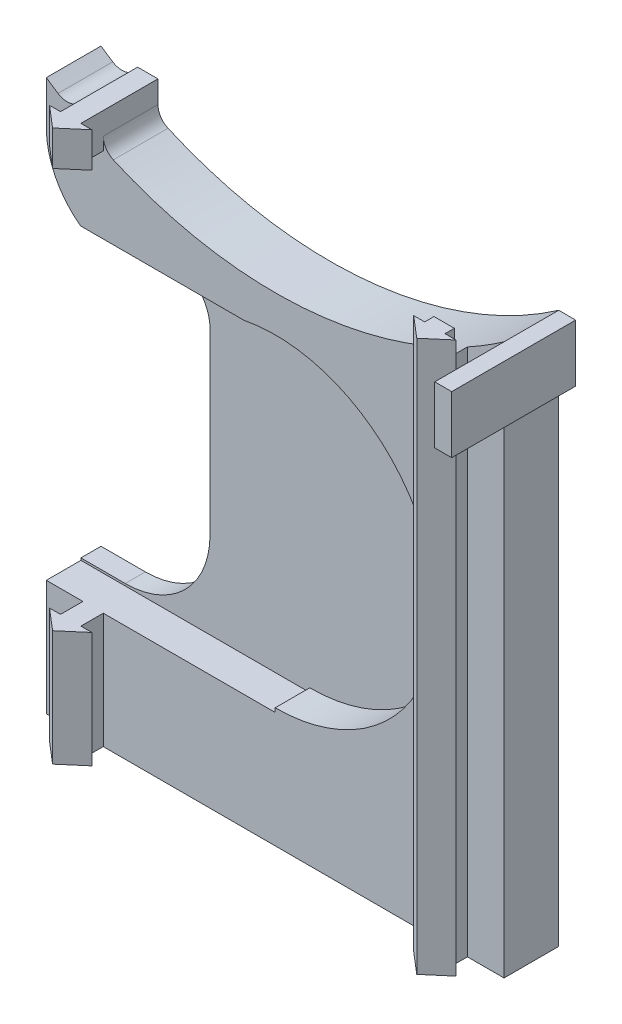
SolidWorks part; units mm, degrees
ref_plane "Alzado" through (0, 0, 0) normal (0, 0, 1) x (1, 0, 0)
ref_plane "Planta" through (0, 0, 0) normal (0, 1, 0) x (1, 0, 0)
ref_plane "Vista lateral" through (0, 0, 0) normal (1, 0, 0) x (0, 0, -1)
sketch "Croquis1" plane through (0, 0, 0) normal (0, 1, 0) x (1, 0, 0)
  line L16 (-22.8311, -9.1001) -> (-21.5393, -9.1001)
  line L17 (-19.1393, -6.4534) -> (-19.1393, -9.1001)
  line L18 (-21.5393, -6.4534) -> (-21.5393, -9.1001)
  line L19 (-19.1393, -9.1001) -> (-17.8476, -9.1001)
  line L20 (-22.8311, -9.1001) -> (-20.3393, -11.2322)
  line L21 (-20.3393, -11.2322) -> (-17.8476, -9.1001)
  line L23 (1.1429, 0) -> (1.1429, -6) construction
  line L35 (-23.6393, -8.8034) -> (-20.3393, -11.627) construction
  line L36 (-20.3393, -11.627) -> (-17.0393, -8.8034) construction
  line L38 (-21.8393, -6.4534) -> (-21.8393, -8.8034) construction
  line L39 (-18.8393, -6.4534) -> (-18.8393, -8.8034) construction
  line L40 (-18.8393, -8.8034) -> (-17.0393, -8.8034) construction
  line L42 (-25.8571, 0) -> (-25.8571, -6.4534)
  line L44 (-25.8571, 0) -> (28.1429, 0)
  line L45 (28.1429, 0) -> (28.1429, -6.4534)
  line L46 (21.4252, -6.4534) -> (21.4252, -9.1001)
  line L47 (21.4252, -9.1001) -> (20.1334, -9.1001)
  line L48 (22.6252, -11.2322) -> (20.1334, -9.1001)
  line L49 (25.117, -9.1001) -> (22.6252, -11.2322)
  line L50 (25.117, -9.1001) -> (23.8252, -9.1001)
  line L51 (23.8252, -6.4534) -> (23.8252, -9.1001)
  line L52 (-25.8571, -6.4534) -> (-21.5393, -6.4534)
  line L53 (-19.1393, -6.4534) -> (21.4252, -6.4534)
  line L54 (23.8252, -6.4534) -> (28.1429, -6.4534)
  point P10 (0, -5.8984)
  point P11 (-20.9906, -10.0474)
  point P24 (-18.6893, -10.2152)
  point P30 (20.9906, -10.0474)
  dimension "D2" = 0.3
  dimension "D4" = 0.3
  dimension "D5" = 0.2967
  dimension "D6" = 0.3
  dimension "D7" = 0.3
extrude "Saliente-Extruir1" add sketch "Croquis1" along normal blind 100
ref_plane "Plane1" through (0, 100, 0) normal (0, 1, 0) x (1, 0, 0)
sketch "Sketch3" plane through (-25.8571, 0, 0) normal (-1, 0, 0) x (0, 0, 1)
  line L1 (13.0991, 86.8623) -> (2.3754, 86.8623)
  line L2 (13.0991, 86.8623) -> (13.0991, 48.6348)
  line L3 (13.0991, 48.6348) -> (2.3754, 48.6348)
  line L4 (2.3754, 86.8623) -> (2.3754, 48.6348)
  point P6 (0, 0)
  point P7 (0, 0)
extrude "Cut-Extrude1" cut sketch "Sketch3" against normal blind 27
sketch "Sketch5" plane through (0, 0, 6.4534) normal (0, 0, 1) x (1, 0, 0)
  line L0 (1.1429, 48.6348) -> (1.1429, 86.8623) construction
  circle A0 centre (1.1429, 68.1655) radius 19.0562
  point P4 (1.1429, 68.1655)
extrude "Cut-Extrude2" cut sketch "Sketch5" against normal up to surface (4.078 mm away) up to face at (-12.3571, 67.7486, 2.3754)
sketch "Sketch6" plane through (0, 0, 0) normal (0, 0, -1) x (-1, 0, 0)
  line L0 (-28.1429, 100) -> (25.8571, 100) construction
  arc A0 (-28.1429, 100) -> (25.8571, 100) centre (-1.1429, 138.7173) ccw
  arc A1 (-28.1429, 100) -> (25.8571, 100) centre (-1.1429, 64.6987) cw
extrude "Cut-Extrude3" cut sketch "Sketch6" against normal blind 8
sketch "Sketch7" plane through (0, 0, 0) normal (0, 0, -1) x (-1, 0, 0)
  line L0 (25.8571, 100) -> (25.8571, 0) construction
  line L1 (25.8571, 48.8854) -> (10.6195, 48.8854)
  line L2 (25.8571, 48.8854) -> (25.8571, 84.8851)
  line L3 (25.8571, 84.8851) -> (10.6195, 84.8851)
  line L4 (10.6195, 48.8854) -> (10.6195, 84.8851)
extrude "Cut-Extrude4" cut sketch "Sketch7" against normal blind 5.8
fillet "Fillet1" radius 10 1 edges at (-25.8571, 84.8851, 1.1877)
fillet "Fillet2" radius 10 1 edges at (-10.6195, 48.8854, 1.1877)
fillet "Fillet3" radius 5 1 edges at (-10.6195, 84.8851, 1.1877)
sketch "Sketch8" plane through (28.1429, 0, 0) normal (1, 0, 0) x (0, 0, -1)
  line L1 (0, 100) -> (-14.627, 100)
  line L2 (0, 100) -> (0, 93.2472)
  line L3 (0, 93.2472) -> (-14.627, 93.2472)
  line L4 (-14.627, 100) -> (-14.627, 93.2472)
  point P7 (0, 0)
  point P8 (0, 0)
extrude "Boss-Extrude1" add sketch "Sketch8" along normal blind 2
sketch "Sketch11" plane through (0, 0, 0) normal (0, 0, -1) x (-1, 0, 0)
  line L0 (-28.1429, 93.2472) -> (-28.1429, 0) construction
  line L1 (25.8571, 0) -> (-28.1429, 0)
  line L2 (25.8571, 0) -> (25.8571, 35)
  line L3 (25.8571, 35) -> (-28.1429, 35)
  line L4 (-28.1429, 0) -> (-28.1429, 35)
  dimension "D1" = 35
extrude "Cut-Extrude6" cut sketch "Sketch11" against normal blind 19
sketch "Sketch12" plane through (0, 86.8623, 0) normal (0, -1, 0) x (1, 0, 0)
  line L1 (-17.7344, 6.4534) -> (-23.2366, 6.4534)
  line L2 (-17.7344, 6.4534) -> (-17.7344, 11.6112)
  line L3 (-17.7344, 11.6112) -> (-23.2366, 11.6112)
  line L4 (-23.2366, 6.4534) -> (-23.2366, 11.6112)
  point P5 (0, 0)
extrude "Cut-Extrude7" cut sketch "Sketch12" against normal blind 9
sketch "Sketch13" plane through (0, 0, 8) normal (0, 0, -1) x (-1, 0, 0)
  line L3 (21.5393, 100) -> (19.1393, 100)
  line L4 (19.1393, 100) -> (19.1393, 96.095)
  line L5 (21.5393, 97.3223) -> (21.5393, 100)
  line L6 (21.5393, 100) -> (19.1393, 100)
  line L7 (19.1393, 100) -> (19.1393, 96.095)
  line L8 (21.5393, 97.3223) -> (21.5393, 100)
  arc A1 (19.1393, 96.095) -> (21.5393, 97.3223) centre (-1.1429, 138.7173) ccw
  arc A2 (19.1393, 96.095) -> (21.5393, 97.3223) centre (-1.1429, 138.7173) ccw
  dimension "D1" = 0
extrude "Boss-Extrude2" add sketch "Sketch13" along normal blind 8
fillet "Fillet4" radius 2 1 edges at (-21.5393, 97.3223, 3.2267)
fillet "Fillet5" radius 2 1 edges at (-19.1393, 96.095, 3.2267)
